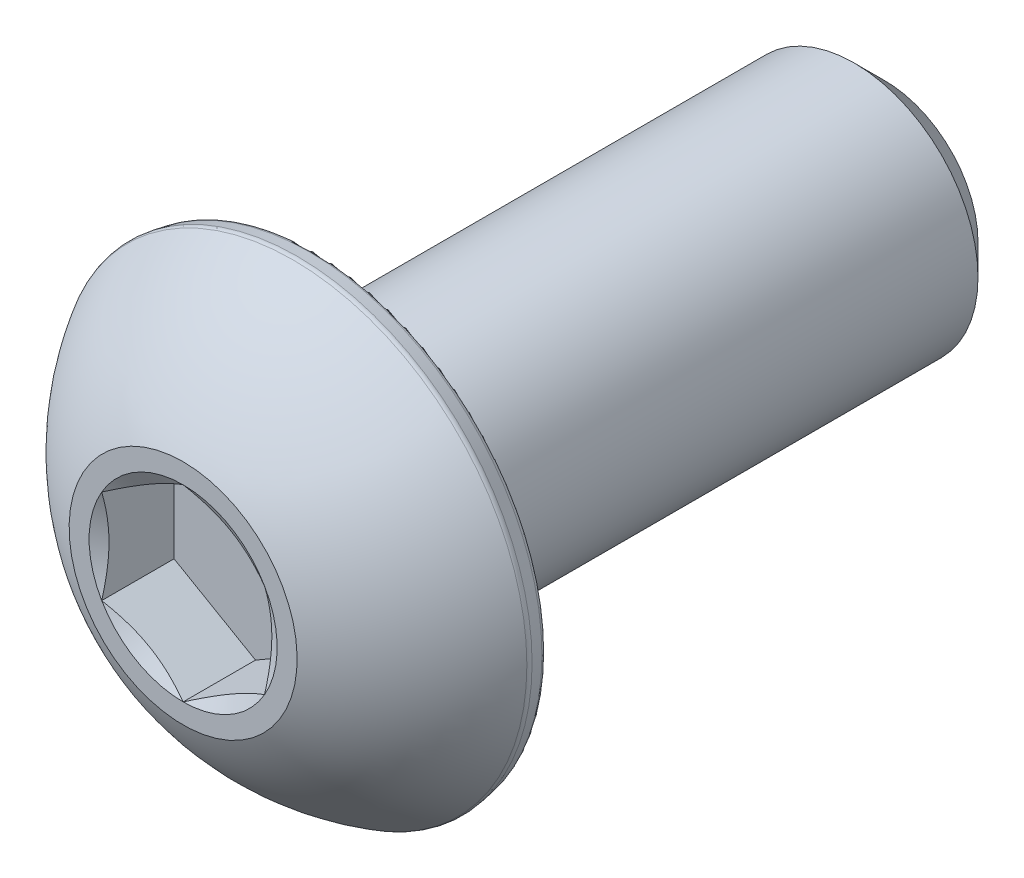
SolidWorks part; units mm, degrees
material "Alloy Steel"
ref_plane "Front Plane" through (0, 0, 0) normal (0, 0, 1) x (1, 0, 0)
ref_plane "Top Plane" through (0, 0, 0) normal (0, 1, 0) x (1, 0, 0)
ref_plane "Right Plane" through (0, 0, 0) normal (1, 0, 0) x (0, 0, -1)
sketch "Sketch1" plane through (0, 0, 0) normal (1, 0, 0) x (0, 0, -1)
  line L0 (-6.8389, 0) -> (6.8389, 0) construction
  line L1 (-6.8389, 0) -> (-6.8389, 4.5847)
  line L2 (-6.8389, 4.5847) -> (-4.2735, 4.5847)
  line L3 (-4.2735, 4.5847) -> (-4.2735, 2.413)
  line L4 (-4.2735, 2.413) -> (6.8389, 2.413)
  line L5 (6.8389, 2.413) -> (6.8389, 0)
  point P2 (0, 0)
  point P4 (6.0452, 0)
  point P9 (5.6483, 2.413)
  point P10 (5.6483, -2.413)
  point P11 (6.8389, -2.413)
  point P15 (-5.428, 0)
  dimension "Head Height" = 2.5654
  dimension "Head Diameter" = 9.1694
  dimension "Length" = 11.1125
  dimension "Screw Size Decimal Equivalent" = 4.826
  dimension "Thread Pitch" = 0.7937
  dimension "D1" = 1.1906
  dimension "D2" = 1.411
sketch "Sketch2" plane through (0, 0, 0) normal (0, 0, 1) x (1, 0, 0)
  line L0 (0, 2.413) -> (0, 0) construction
  line L1 (0, 1.8331) -> (-1.5875, 0.9165)
  line L2 (-1.5875, 0.9165) -> (-1.5875, -0.9165)
  line L3 (-1.5875, -0.9165) -> (0, -1.8331)
  line L4 (0, -1.8331) -> (1.5875, -0.9165)
  line L5 (1.5875, -0.9165) -> (1.5875, 0.9165)
  line L6 (1.5875, 0.9165) -> (0, 1.8331)
  circle A0 centre (0, 0) radius 1.5875 construction
  circle A1 centre (0, 0) radius 2.2225
  point P10 (0, 2.2225)
  dimension "D1" = 4.445
  dimension "Drive Size" = 3.175
sketch "Sketch3" plane through (0, 0, 0) normal (1, 0, 0) x (0, 0, -1)
  line L0 (-6.8389, 0) -> (-6.8389, 2.2225)
  line L1 (-6.8389, 0) -> (-6.8389, 4.5847) construction
  line L2 (-6.8389, 4.5847) -> (-4.2735, 4.5847) construction
  line L3 (-4.6584, 4.5847) -> (-4.2735, 4.5168)
  line L4 (-4.2735, 4.5847) -> (-4.2735, 2.413) construction
  line L5 (-4.2735, 4.5168) -> (-4.2735, 2.413)
  line L6 (-6.8389, 0) -> (6.8389, 0) construction
  line L7 (-6.8389, 0) -> (6.8389, 0)
  line L8 (6.8389, 0) -> (6.8389, 1.8177)
  line L9 (6.8389, 2.413) -> (6.8389, 0) construction
  line L10 (6.8389, 1.8177) -> (6.2436, 2.413)
  line L11 (-4.2735, 2.413) -> (6.8389, 2.413) construction
  line L12 (6.2436, 2.413) -> (-4.2735, 2.413)
  arc A0 (-6.8389, 2.2225) -> (-4.6584, 4.5847) centre (-2.0616, 0) cw
  dimension "D1" = 0.3848
  dimension "D2" = 10
  dimension "D3" = 45
  dimension "D4" = 0.5953
revolve "Revolve1" add sketch "Sketch3" angle 360 about L7
sketch "Sketch4" plane through (0, 0, 6.8389) normal (0, 0, 1) x (1, 0, 0)
  line L0 (-1.5875, -0.9165) -> (0, -1.8331) construction
  line L1 (-1.5875, 0.9165) -> (-1.5875, -0.9165) construction
  line L2 (0, 1.8331) -> (-1.5875, 0.9165) construction
  line L3 (1.5875, 0.9165) -> (0, 1.8331) construction
  line L4 (1.5875, -0.9165) -> (1.5875, 0.9165) construction
  line L5 (0, -1.8331) -> (1.5875, -0.9165) construction
  line L6 (-1.5875, -0.9165) -> (0, -1.8331)
  line L7 (-1.5875, 0.9165) -> (-1.5875, -0.9165)
  line L8 (0, 1.8331) -> (-1.5875, 0.9165)
  line L9 (1.5875, 0.9165) -> (0, 1.8331)
  line L10 (1.5875, -0.9165) -> (1.5875, 0.9165)
  line L11 (0, -1.8331) -> (1.5875, -0.9165)
extrude "Cut-Extrude1" cut sketch "Sketch4" against normal up to vertex (1.411 mm away) up to point (0, 0, 5.428)
sketch "Sketch5" plane through (0, 0, 6.8389) normal (0, 0, 1) x (1, 0, 0)
  circle A0 centre (0, 0) radius 1.8331
extrude "Cut-Extrude2" cut sketch "Sketch5" against normal up to vertex (1.411 mm away) draft 60 up to point (0, 0, 5.428)
fillet "Fillet1" radius 0.1283 2 edges at (4.5847, 0, 4.6584) (4.5168, 0, 4.2735)
split "Split1" [suppressed] bodies to split 106
sketch "Sketch6" [suppressed] plane through (0, 0, -7.6327) normal (0, 0, -1) x (-1, 0, 0)
  circle A0 centre (0, 0) radius 2.413 construction
  circle A1 centre (0, 0) radius 2.413
curve "Helix/Spiral1" [suppressed]
sketch "Sketch7" [suppressed] plane through (0, 0, 0) normal (1, 0, 0) x (0, 0, -1)
  line L0 (7.5831, 2.4989) -> (7.98, 1.8115) construction
  line L1 (7.98, 1.8115) -> (8.3768, 2.4989) construction
  line L2 (8.3768, 2.4989) -> (7.5831, 2.4989) construction
  line L3 (7.6079, 2.456) -> (8.352, 2.456)
  line L4 (8.352, 2.456) -> (8.0296, 1.8974)
  line L5 (8.0296, 1.8974) -> (7.9304, 1.8974)
  line L6 (7.9304, 1.8974) -> (7.6079, 2.456)
  line L7 (7.98, 1.8974) -> (7.98, 1.8115) construction
  line L8 (7.6327, 2.413) -> (8.3272, 2.413) construction
  line L9 (7.98, 2.4989) -> (7.98, 2.413) construction
  point P12 (7.98, 2.456)
  dimension "D1" = 0.7937
  dimension "D2" = 0.0992
sweep "Cut-Sweep1" [suppressed] cut profiles "Sketch7" path "Helix/Spiral1"
sketch "Sketch8" [suppressed] plane through (0, 0, 5.0673) normal (0, 0, -1) x (-1, 0, 0)
  circle A0 centre (0, 0) radius 2.4989
extrude "Boss-Extrude1" [suppressed] add sketch "Sketch8" along normal up to vertex draft 45 up to point (0, 2.413, -5.6483)
equation "\"D1@Sketch1\"=\"Thread Pitch@Sketch1\"*1.5"
equation "\"D2@Sketch1\"=0.55*\"Head Height@Sketch1\""
equation "\"D1@Sketch2\"=\"Drive Size@Sketch2\"*1.4"
equation "\"D1@Sketch3\"=0.15*\"Head Height@Sketch1\""
equation "\"D4@Sketch3\"=0.75*\"Thread Pitch@Sketch1\""
equation "\"D1@Fillet1\"=.05*\"Head Height@Sketch1\""
equation "\"D4@Helix/Spiral1\"=\"Thread Pitch@Sketch1\""
equation "\"D3@Helix/Spiral1\"=\"Length@Sketch1\"+\"Thread Pitch@Sketch1\""
equation "\"D2@Sketch7\"=\"D1@Sketch7\"/8"
equation "\"D1@Sketch7\"=\"Thread Pitch@Sketch1\""
